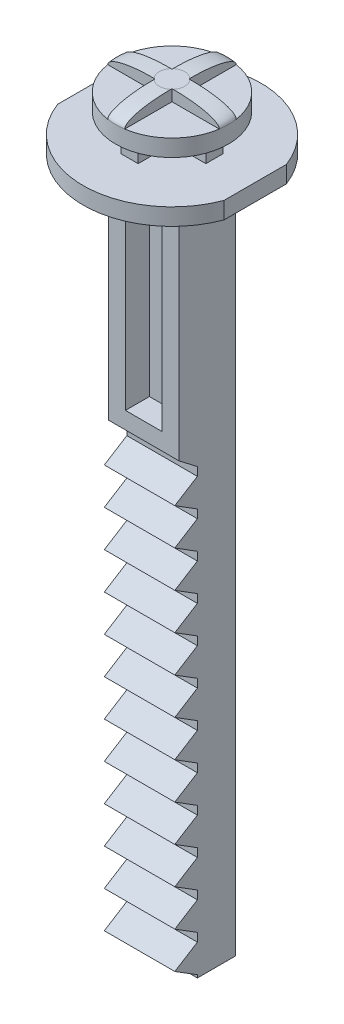
SolidWorks part; units mm, degrees
ref_plane "Front Plane" through (0, 0, 0) normal (0, 0, 1) x (1, 0, 0)
ref_plane "Top Plane" through (0, 0, 0) normal (0, 1, 0) x (1, 0, 0)
ref_plane "Right Plane" through (0, 0, 0) normal (1, 0, 0) x (0, 0, -1)
sketch "Sketch1" plane through (0, 0, 0) normal (0, 1, 0) x (1, 0, 0)
  circle A0 centre (0, 0) radius 6.3
  dimension "D1" = 12.6
extrude "Boss-Extrude1" add sketch "Sketch1" along normal blind 1.2
sketch "Sketch2" plane through (0, 1.2, 0) normal (0, 1, 0) x (1, 0, 0)
  line L1 (0.6, -3) -> (-0.6, -3)
  line L2 (0.6, -3) -> (0.6, 3)
  line L3 (0.6, 3) -> (-0.6, 3)
  line L4 (-0.6, -3) -> (-0.6, 3)
  line L5 (0.6, -3) -> (-0.6, 3) construction
  line L6 (0.6, 3) -> (-0.6, -3) construction
  line L7 (3, -0.6) -> (-3, -0.6)
  line L8 (3, -0.6) -> (3, 0.6)
  line L9 (3, 0.6) -> (-3, 0.6)
  line L10 (-3, -0.6) -> (-3, 0.6)
  line L11 (3, -0.6) -> (-3, 0.6) construction
  line L12 (3, 0.6) -> (-3, -0.6) construction
  point P0 (0, 0)
  point P6 (0, 0)
  dimension "D1" = 1.2
  dimension "D2" = 6
extrude "Boss-Extrude2" add sketch "Sketch2" along normal blind 1.4 contours L2 L3 L4 L1 | L7 L10 L9 L8
sketch "Sketch3" plane through (0, 2.6, 0) normal (0, 1, 0) x (1, 0, 0)
  circle A0 centre (0, 0) radius 4
  dimension "D1" = 8
extrude "Boss-Extrude3" add sketch "Sketch3" along normal blind 1.2
sketch "Sketch4" plane through (0, 3.8, 0) normal (0, 1, 0) x (1, 0, 0)
  line L1 (0.6, -4) -> (-0.6, -4)
  line L2 (0.6, -4) -> (0.6, 4)
  line L3 (0.6, 4) -> (-0.6, 4)
  line L4 (-0.6, -4) -> (-0.6, 4)
  line L5 (0.6, -4) -> (-0.6, 4) construction
  line L6 (0.6, 4) -> (-0.6, -4) construction
  line L7 (4, -0.6) -> (-4, -0.6)
  line L8 (4, -0.6) -> (4, 0.6)
  line L9 (4, 0.6) -> (-4, 0.6)
  line L10 (-4, -0.6) -> (-4, 0.6)
  line L11 (4, -0.6) -> (-4, 0.6) construction
  line L12 (4, 0.6) -> (-4, -0.6) construction
  circle A0 centre (0, 0) radius 4 construction
  point P0 (0, 0)
  point P8 (0, 0)
  circle M8 centre (0, 0) radius 4
  dimension "D1" = 1.2
extrude "Boss-Extrude4" add sketch "Sketch4" along normal blind 0.8 contours L9 L2 L7 M8 | L2 L9 L4 L7 | L2 L7 L4 M8 | L4 L9 L7 M8 | L9 L2 L4 M8 region at (0, 3.8, 2.2925) region at (0, 3.8, 0) region at (2.2925, 3.8, 0) region at (-2.2925, 3.8, 0) region at (0, 3.8, -2.2925)
fillet "Fillet1" radius 0.8 4 edges at (0, 4.6, 4) (-4, 4.6, 0) (4, 4.6, 0) (0, 4.6, -4) second distance 3.1 first distance on face at (0, 4.2, 0)
sketch "Sketch5" plane through (0, 0, 0) normal (0, -1, 0) x (-1, 0, 0)
  line L1 (-5.9, 5.9) -> (5.9, 5.9) construction
  line L2 (-5.9, 5.9) -> (-5.9, -5.9) construction
  line L3 (-5.9, -5.9) -> (5.9, -5.9) construction
  line L4 (5.9, 5.9) -> (5.9, -5.9) construction
  line L5 (-5.9, 5.9) -> (5.9, -5.9) construction
  line L6 (-5.9, -5.9) -> (5.9, 5.9) construction
  line L7 (5.9, -5.9) -> (6.9, -5.9)
  line L8 (5.9, -5.9) -> (5.9, 5.9)
  line L9 (5.9, 5.9) -> (6.9, 5.9)
  line L10 (6.9, -5.9) -> (6.9, 5.9)
  line L11 (-5.9, -5.9) -> (-6.9, -5.9)
  line L12 (-5.9, -5.9) -> (-5.9, 5.9)
  line L13 (-5.9, 5.9) -> (-6.9, 5.9)
  line L14 (-6.9, -5.9) -> (-6.9, 5.9)
  point P0 (0, 0)
  dimension "D1" = 11.8
  dimension "D2" = 1
extrude "Cut-Extrude1" cut sketch "Sketch5" against normal up to surface (1.2 mm away) up to face at (0, 1.2, 6.3)
sketch "Sketch6" plane through (0, 0, 0) normal (0, -1, 0) x (-1, 0, 0)
  line L1 (-2.5, 2) -> (2.5, 2)
  line L2 (-2.5, 2) -> (-2.5, -2)
  line L3 (-2.5, -2) -> (2.5, -2)
  line L4 (2.5, 2) -> (2.5, -2)
  line L5 (-2.5, 2) -> (2.5, -2) construction
  line L6 (-2.5, -2) -> (2.5, 2) construction
  point P0 (0, 0)
  dimension "D1" = 5
  dimension "D2" = 4
extrude "Boss-Extrude5" add sketch "Sketch6" along normal blind 49
sketch "Sketch7" plane through (0, 0, 2) normal (0, 0, 1) x (1, 0, 0)
  line L0 (2.5, 0) -> (-2.5, 0) construction
  line L1 (-1.3, 0) -> (1.3, 0)
  line L2 (-1.3, 0) -> (-1.3, -15.4)
  line L3 (-1.3, -15.4) -> (1.3, -15.4)
  line L4 (1.3, 0) -> (1.3, -15.4)
  line L6 (0, 0) -> (0, 50000) construction
  line L7 (5.9, 1.2) -> (-5.9, 1.2) construction
  point P13 (0, 1.2)
  dimension "D1" = 15.4
  dimension "D2" = 2.6
extrude "Cut-Extrude2" cut sketch "Sketch7" against normal blind 1.7
sketch "Sketch8" plane through (0, 0, -2) normal (0, 0, -1) x (-1, 0, 0)
  line L0 (2.5, 0) -> (-2.5, 0) construction
  line L1 (-1.3, 0) -> (1.3, 0)
  line L2 (-1.3, 0) -> (-1.3, -12.6)
  line L3 (-1.3, -12.6) -> (1.3, -12.6)
  line L4 (1.3, 0) -> (1.3, -12.6)
  line L5 (0, 0) -> (0, 50000) construction
  line L6 (5.9, 1.2) -> (-5.9, 1.2) construction
  line L9 (2.5, -49) -> (-2.5, -49) construction
  line L10 (-1.3, -12.6) -> (1.3, -12.6) construction
  line L11 (-1.3, -12.6) -> (-1.3, -13.8) construction
  line L12 (-1.3, -13.8) -> (1.3, -13.8) construction
  line L13 (1.3, -12.6) -> (1.3, -13.8) construction
  line L14 (-1.3, -13.8) -> (1.3, -13.8)
  line L15 (-1.3, -13.8) -> (-1.3, -49)
  line L16 (-1.3, -49) -> (1.3, -49)
  line L17 (1.3, -13.8) -> (1.3, -49)
  point P11 (0, 1.2)
  line M2 (2.5, 0) -> (-2.5, 0)
  line M4 (-2.5, -49) -> (2.5, -49)
  dimension "D1" = 2.6
  dimension "D2" = 12.6
  dimension "D3" = 1.2
extrude "Cut-Extrude3" cut sketch "Sketch8" against normal blind 1.2 contours L4 L2 L3 M2 | L17 L14 L15 M4 region at (0, -6.3, -2) region at (0, -31.4, -2)
ref_plane "Plane1" through (0, -12.6, 0) normal (0, 1, 0) x (1, 0, 0)
sketch "Sketch12" plane through (0, -12.6, 0) normal (0, 1, 0) x (1, 0, 0)
  line L2 (-2.5, 2) -> (2.5, 2) construction
  line L3 (-2.5, 2) -> (-2.5, 2.8) construction
  line L4 (-2.5, 2.8) -> (2.5, 2.8) construction
  line L5 (2.5, 2) -> (2.5, 2.8) construction
  line L13 (-1.3, 2) -> (-2.5, 2)
  line L14 (-1.3, 0.8) -> (-1.3, 2)
  line L15 (1.3, 0.8) -> (-1.3, 0.8)
  line L16 (1.3, 2) -> (1.3, 0.8)
  line L17 (2.5, 2) -> (1.3, 2)
  line L18 (2.5, -2) -> (2.5, 2)
  line L19 (-2.5, -2) -> (2.5, -2)
  line L20 (-2.5, 2) -> (-2.5, -2)
  line L21 (-1.3, 2) -> (-2.5, 2)
  line L22 (-1.3, 0.8) -> (-1.3, 2)
  line L23 (1.3, 0.8) -> (-1.3, 0.8)
  line L24 (1.3, 2) -> (1.3, 0.8)
  line L25 (2.5, 2) -> (1.3, 2)
  arc A0 (-2.5, 2) -> (2.5, 2) centre (0, -1.5062) cw
  dimension "D1" = 0.8
  dimension "D2" = 0
extrude "Boss-Extrude6" add sketch "Sketch12" against normal blind 1.2
sketch "Sketch13" plane through (0, 0, 2) normal (0, 0, 1) x (1, 0, 0)
  line L0 (1.3, -15.4) -> (1.3, 0) construction
  line L1 (-1.3, -15.4) -> (1.3, -15.4) construction
  line L2 (-1.3, -15.4) -> (-1.3, -16.6) construction
  line L3 (-1.3, -16.6) -> (1.3, -16.6) construction
  line L4 (1.3, -15.4) -> (1.3, -16.6) construction
  line L5 (-2.5, -49) -> (-2.5, 0) construction
  line L6 (-2.5, -16.6) -> (2.5, -16.6)
  line L7 (-2.5, -16.6) -> (-2.5, -49)
  line L8 (-2.5, -49) -> (2.5, -49)
  line L9 (2.5, -16.6) -> (2.5, -49)
  line L10 (2.5, -49) -> (2.5, 0) construction
  line L11 (2.5, -49) -> (-2.5, -49) construction
  dimension "D1" = 1.2
extrude "Cut-Extrude4" cut sketch "Sketch13" against normal blind 1.3
ref_plane "Plane2" through (2.5, 0, 0) normal (1, 0, 0) x (0, 0, -1)
sketch "Sketch14" plane through (2.5, 0, 0) normal (1, 0, 0) x (0, 0, -1)
  line L0 (-0.7, -46.8) -> (-0.7, -48.8)
  line L1 (-0.7, -49) -> (-0.7, -16.6) construction
  line L2 (-0.7, -48.8) -> (-2.3, -47.8)
  line L3 (-2.3, -47.8) -> (-0.7, -46.8)
  line L4 (2, -49) -> (-0.7, -49) construction
  line L38 (-2.3, -45.2) -> (-0.7, -44.2)
  line L39 (-0.7, -44.2) -> (-0.7, -46.2)
  line L40 (-0.7, -46.2) -> (-2.3, -45.2)
  line L41 (-2.3, -42.6) -> (-0.7, -41.6)
  line L42 (-0.7, -41.6) -> (-0.7, -43.6)
  line L43 (-0.7, -43.6) -> (-2.3, -42.6)
  line L44 (-2.3, -40) -> (-0.7, -39)
  line L45 (-0.7, -39) -> (-0.7, -41)
  line L46 (-0.7, -41) -> (-2.3, -40)
  line L47 (-2.3, -37.4) -> (-0.7, -36.4)
  line L48 (-0.7, -36.4) -> (-0.7, -38.4)
  line L49 (-0.7, -38.4) -> (-2.3, -37.4)
  line L50 (-2.3, -34.8) -> (-0.7, -33.8)
  line L51 (-0.7, -33.8) -> (-0.7, -35.8)
  line L52 (-0.7, -35.8) -> (-2.3, -34.8)
  line L53 (-2.3, -32.2) -> (-0.7, -31.2)
  line L54 (-0.7, -31.2) -> (-0.7, -33.2)
  line L55 (-0.7, -33.2) -> (-2.3, -32.2)
  line L56 (-2.3, -29.6) -> (-0.7, -28.6)
  line L57 (-0.7, -28.6) -> (-0.7, -30.6)
  line L58 (-0.7, -30.6) -> (-2.3, -29.6)
  line L59 (-2.3, -27) -> (-0.7, -26)
  line L60 (-0.7, -26) -> (-0.7, -28)
  line L61 (-0.7, -28) -> (-2.3, -27)
  line L62 (-2.3, -24.4) -> (-0.7, -23.4)
  line L63 (-0.7, -23.4) -> (-0.7, -25.4)
  line L64 (-0.7, -25.4) -> (-2.3, -24.4)
  line L65 (-2.3, -21.8) -> (-0.7, -20.8)
  line L66 (-0.7, -20.8) -> (-0.7, -22.8)
  line L67 (-0.7, -22.8) -> (-2.3, -21.8)
  line L68 (-2.3, -19.2) -> (-0.7, -18.2)
  line L69 (-0.7, -18.2) -> (-0.7, -20.2)
  line L70 (-0.7, -20.2) -> (-2.3, -19.2)
  line L71 (-0.7, -17.6) -> (-2, -16.6)
  line L72 (-0.7, -18.2) -> (-2.3, -18.2) construction
  line L73 (-0.7, -18.2) -> (-0.7, -17.6) construction
  line L74 (-0.7, -17.6) -> (-2.3, -17.6) construction
  line L75 (-2.3, -18.2) -> (-2.3, -17.6) construction
  line L77 (-0.7, -17.6) -> (-0.7, -16.6)
  line L78 (-0.7, -16.6) -> (-2, -16.6)
  dimension "D1" = 1.6
  dimension "D2" = 2
  dimension "D3" = 0.2
  dimension "D5" = 0.6
  dimension "D6" = 1.6
  dimension "D4" = 12
extrude "Boss-Extrude7" add sketch "Sketch14" against normal blind 5
ref_plane "Plane3" through (0, -15.4, 0) normal (0, 1, 0) x (1, 0, 0)
ref_plane "Plane4" through (0, -16.45, 0) normal (0, 1, 0) x (1, 0, 0)
